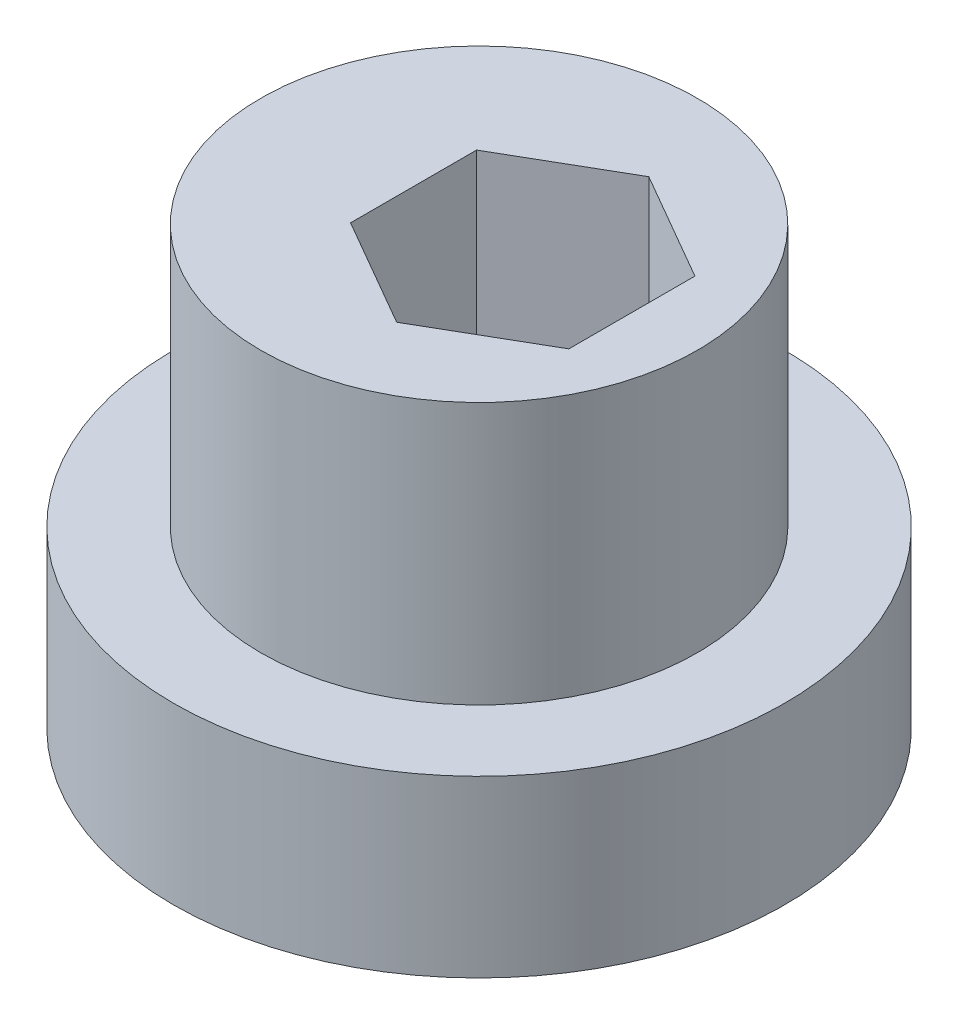
SolidWorks part; units mm, degrees
ref_plane "Front Plane" through (0, 0, 0) normal (0, 0, 1) x (1, 0, 0)
ref_plane "Top Plane" through (0, 0, 0) normal (0, 1, 0) x (1, 0, 0)
ref_plane "Right Plane" through (0, 0, 0) normal (1, 0, 0) x (0, 0, -1)
sketch "Sketch1" plane through (0, 0, 0) normal (0, 1, 0) x (1, 0, 0)
  circle A0 centre (0, 0) radius 7
  dimension "D1" = 14
extrude "Boss-Extrude1" add sketch "Sketch1" along normal blind 4
sketch "Sketch2" plane through (0, 4, 0) normal (0, 1, 0) x (1, 0, 0)
  circle A0 centre (0, 0) radius 5
  dimension "D1" = 10
extrude "Boss-Extrude2" add sketch "Sketch2" along normal blind 6
sketch "Sketch3" plane through (0, 10, 0) normal (0, 1, 0) x (1, 0, 0)
  line L1 (3.5, -1.4434) -> (3.5, 1.4434)
  line L2 (3.5, 1.4434) -> (1, 2.8868)
  line L3 (1, 2.8868) -> (-1.5, 1.4434)
  line L4 (-1.5, 1.4434) -> (-1.5, -1.4434)
  line L5 (-1.5, -1.4434) -> (1, -2.8868)
  line L6 (1, -2.8868) -> (3.5, -1.4434)
  circle A0 centre (1, 0) radius 2.5 construction
  dimension "D1" = 5
  dimension "D2" = 1
extrude "Cut-Extrude1" cut sketch "Sketch3" against normal through all
sketch "Sketch4" [suppressed] plane through (0, 11, 0) normal (0, 1, 0) x (1, 0, 0)
  line L1 (2.5, 1.4434) -> (0, 2.8868)
  line L2 (0, 2.8868) -> (-2.5, 1.4434)
  line L3 (-2.5, 1.4434) -> (-2.5, -1.4434)
  line L4 (-2.5, -1.4434) -> (0, -2.8868)
  line L5 (0, -2.8868) -> (2.5, -1.4434)
  line L6 (2.5, -1.4434) -> (2.5, 1.4434)
  circle A0 centre (0, 0) radius 2.5 construction
  dimension "D1" = 5
extrude "Cut-Extrude2" [suppressed] cut sketch "Sketch4" against normal through all
equation "\"R_ROLL\"= 5mm"
equation "\"D_SUN\"= 80mm"
equation "\"NUM_ROLL\"= 16"
equation "\"RHO\"= 1mm"
equation "\"D_SHAFT\"= 15mm"
equation "\"D_OUTPUT\"= 40mm"
equation "\"NUM_OUT\"= 6"
equation "\"R_OUT_ROLL\"= 5mm"
